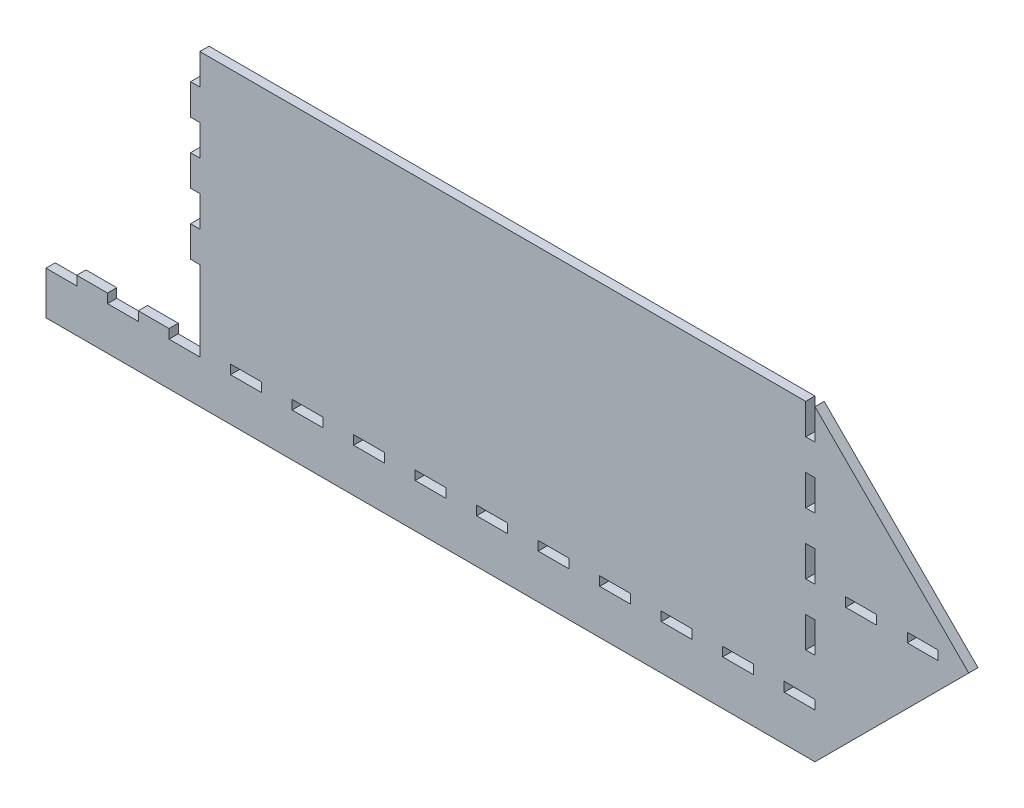
SolidWorks part; units mm, degrees
ref_plane "Front Plane" through (0, 0, 0) normal (0, 0, 1) x (1, 0, 0)
ref_plane "Top Plane" through (0, 0, 0) normal (0, 1, 0) x (1, 0, 0)
ref_plane "Right Plane" through (0, 0, 0) normal (1, 0, 0) x (0, 0, -1)
sketch "Sketch1" plane through (0, 0, 0) normal (0, 0, 1) x (1, 0, 0)
  line L0 (-112.631, -67.7284) -> (-112.631, -53.7284)
  line L1 (-62.631, 22.2716) -> (-65.631, 22.2716)
  line L2 (-102.631, -50.7284) -> (-92.631, -50.7284)
  line L3 (-62.631, 32.2716) -> (137.369, 32.2716)
  line L4 (137.369, 32.2716) -> (187.369, -17.7284)
  line L5 (187.369, -17.7284) -> (137.369, -67.7284)
  line L6 (137.369, -67.7284) -> (-112.631, -67.7284)
  line L7 (-65.631, 22.2716) -> (-65.631, 12.2716)
  line L8 (-62.631, -50.7284) -> (-62.631, -27.7284)
  line L9 (137.369, 32.2716) -> (137.369, -67.7284) construction
  line L10 (137.369, -17.7284) -> (187.369, -17.7284) construction
  line L11 (157.369, -16.2284) -> (147.369, -16.2284)
  line L12 (177.369, -16.2284) -> (167.369, -16.2284)
  line L13 (177.369, -16.2284) -> (177.369, -19.2284)
  line L14 (177.369, -19.2284) -> (167.369, -19.2284)
  line L15 (167.369, -16.2284) -> (167.369, -19.2284)
  line L16 (177.369, -16.2284) -> (167.369, -19.2284) construction
  line L17 (177.369, -19.2284) -> (167.369, -16.2284) construction
  line L18 (157.369, -16.2284) -> (157.369, -19.2284)
  line L19 (157.369, -19.2284) -> (147.369, -19.2284)
  line L20 (147.369, -16.2284) -> (147.369, -19.2284)
  line L21 (137.369, -50.1685) -> (127.369, -50.0127)
  line L22 (137.369, -50.1685) -> (137.369, -53.1358)
  line L23 (137.369, -53.1358) -> (127.369, -53.1358)
  line L24 (127.369, -50.0127) -> (127.369, -53.1358)
  line L25 (137.369, -50.1685) -> (127.369, -53.1358) construction
  line L26 (137.369, -53.1358) -> (127.369, -50.0127) construction
  line L27 (117.369, -50.1845) -> (107.369, -50.1845)
  line L28 (117.369, -50.1845) -> (117.369, -53.1845)
  line L29 (117.369, -53.1845) -> (107.369, -53.1845)
  line L30 (107.369, -50.1845) -> (107.369, -53.1845)
  line L31 (117.369, -50.1845) -> (107.369, -53.1845) construction
  line L32 (117.369, -53.1845) -> (107.369, -50.1845) construction
  line L33 (97.369, -50.2525) -> (87.369, -50.2525)
  line L34 (97.369, -50.2525) -> (97.369, -53.2525)
  line L35 (97.369, -53.2525) -> (87.369, -53.2525)
  line L36 (87.369, -50.2525) -> (87.369, -53.2525)
  line L37 (97.369, -50.2525) -> (87.369, -53.2525) construction
  line L38 (97.369, -53.2525) -> (87.369, -50.2525) construction
  line L39 (77.369, -50.3205) -> (67.369, -50.3205)
  line L40 (77.369, -50.3205) -> (77.369, -53.3205)
  line L41 (77.369, -53.3205) -> (67.369, -53.3205)
  line L42 (67.369, -50.3205) -> (67.369, -53.3205)
  line L43 (77.369, -50.3205) -> (67.369, -53.3205) construction
  line L44 (77.369, -53.3205) -> (67.369, -50.3205) construction
  line L45 (57.369, -50.3885) -> (47.369, -50.3885)
  line L46 (57.369, -50.3885) -> (57.369, -53.3885)
  line L47 (57.369, -53.3885) -> (47.369, -53.3885)
  line L48 (47.369, -50.3885) -> (47.369, -53.3885)
  line L49 (57.369, -50.3885) -> (47.369, -53.3885) construction
  line L50 (57.369, -53.3885) -> (47.369, -50.3885) construction
  line L51 (37.369, -50.4564) -> (27.369, -50.4564)
  line L52 (37.369, -50.4564) -> (37.369, -53.4564)
  line L53 (37.369, -53.4564) -> (27.369, -53.4564)
  line L54 (27.369, -50.4564) -> (27.369, -53.4564)
  line L55 (37.369, -50.4564) -> (27.369, -53.4564) construction
  line L56 (37.369, -53.4564) -> (27.369, -50.4564) construction
  line L57 (17.369, -50.5244) -> (7.369, -50.5244)
  line L58 (17.369, -50.5244) -> (17.369, -53.5244)
  line L59 (17.369, -53.5244) -> (7.369, -53.5244)
  line L60 (7.369, -50.5244) -> (7.369, -53.5244)
  line L61 (17.369, -50.5244) -> (7.369, -53.5244) construction
  line L62 (17.369, -53.5244) -> (7.369, -50.5244) construction
  line L63 (-2.631, -50.5924) -> (-12.631, -50.5924)
  line L64 (-2.631, -50.5924) -> (-2.631, -53.5924)
  line L65 (-2.631, -53.5924) -> (-12.631, -53.5924)
  line L66 (-12.631, -50.5924) -> (-12.631, -53.5924)
  line L67 (-2.631, -50.5924) -> (-12.631, -53.5924) construction
  line L68 (-2.631, -53.5924) -> (-12.631, -50.5924) construction
  line L69 (-22.631, -50.6604) -> (-32.631, -50.6604)
  line L70 (-22.631, -50.6604) -> (-22.631, -53.6604)
  line L71 (-22.631, -53.6604) -> (-32.631, -53.6604)
  line L72 (-32.631, -50.6604) -> (-32.631, -53.6604)
  line L73 (-22.631, -50.6604) -> (-32.631, -53.6604) construction
  line L74 (-22.631, -53.6604) -> (-32.631, -50.6604) construction
  line L75 (-42.631, -50.7284) -> (-52.631, -50.7284)
  line L76 (-42.631, -50.7284) -> (-42.631, -53.7284)
  line L77 (-42.631, -53.7284) -> (-52.631, -53.7284)
  line L78 (-52.631, -50.7284) -> (-52.631, -53.7284)
  line L79 (-42.631, -50.7284) -> (-52.631, -53.7284) construction
  line L80 (-42.631, -53.7284) -> (-52.631, -50.7284) construction
  line L81 (-82.631, -50.7284) -> (-72.631, -50.7284)
  line L82 (-62.631, -50.7284) -> (-62.631, -53.7284)
  line L83 (-62.631, -53.7284) -> (-72.631, -53.7284)
  line L84 (-72.631, -50.7284) -> (-72.631, -53.7284)
  line L85 (-62.631, -50.7284) -> (-72.631, -53.7284) construction
  line L86 (-62.631, -53.7284) -> (-72.631, -50.7284) construction
  line L87 (137.369, 12.2716) -> (134.369, 12.2716)
  line L88 (-82.631, -50.7284) -> (-82.631, -53.7284)
  line L89 (-82.631, -53.7284) -> (-92.631, -53.7284)
  line L90 (-92.631, -50.7284) -> (-92.631, -53.7284)
  line L91 (-82.631, -50.7284) -> (-92.631, -53.7284) construction
  line L92 (-82.631, -53.7284) -> (-92.631, -50.7284) construction
  line L93 (137.369, 32.2716) -> (134.369, 32.2716)
  line L94 (-102.631, -50.7284) -> (-102.631, -53.7284)
  line L95 (-102.631, -53.7284) -> (-112.631, -53.7284)
  line L96 (-65.631, 12.2716) -> (-62.631, 12.2716)
  line L97 (-102.631, -50.7284) -> (-112.631, -53.7284) construction
  line L98 (-102.631, -53.7284) -> (-112.631, -50.7284) construction
  line L99 (-62.631, -50.7284) -> (-72.631, -50.7284) [skipped]
  line L100 (-82.631, -50.7284) -> (-92.631, -50.7284) [skipped]
  line L101 (-102.631, -50.7284) -> (-112.631, -50.7284) [skipped]
  line L102 (137.369, 32.2716) -> (137.369, 22.2716)
  line L103 (137.369, 22.2716) -> (134.369, 22.2716)
  line L104 (134.369, 32.2716) -> (134.369, 22.2716)
  line L105 (137.369, 12.2716) -> (137.369, 2.2716)
  line L106 (137.369, 2.2716) -> (134.369, 2.2716)
  line L107 (134.369, 12.2716) -> (134.369, 2.2716)
  line L108 (137.369, -7.7284) -> (134.369, -7.7284)
  line L109 (137.369, -7.7284) -> (137.369, -17.7284)
  line L110 (-62.631, 2.2716) -> (-65.631, 2.2716)
  line L111 (137.369, -17.7284) -> (134.369, -17.7284)
  line L113 (-65.631, 2.2716) -> (-65.631, -7.7284)
  line L114 (157.369, -16.2284) -> (147.369, -19.2284) construction
  line L115 (-65.631, -7.7284) -> (-62.631, -7.7284)
  line L116 (-62.631, 2.2716) -> (-62.631, 12.2716)
  line L117 (-62.631, -17.7284) -> (-65.631, -17.7284)
  line L118 (-65.631, -17.7284) -> (-65.631, -27.7284)
  line L119 (-65.631, -27.7284) -> (-62.631, -27.7284)
  line L120 (-62.631, -17.7284) -> (-62.631, -7.7284)
  line L121 (134.369, -7.7284) -> (134.369, -17.7284)
  line L122 (157.369, -19.2284) -> (147.369, -16.2284) construction
  line L123 (-62.631, 22.2716) -> (-62.631, 32.2716)
  line L125 (-112.631, -52.2284) -> (-112.631, -53.3547) [skipped]
  line L128 (137.369, -27.7284) -> (134.369, -27.7284)
  line L129 (137.369, -27.7284) -> (137.369, -37.7284)
  line L130 (137.369, -37.7284) -> (134.369, -37.7284)
  line L131 (134.369, -27.7284) -> (134.369, -37.7284)
  point P5 (172.369, -17.7284)
  point P9 (151.1235, -51.5486)
  point P17 (152.369, -17.7284)
  point P19 (131.1235, -51.6165)
  point P24 (111.1235, -51.6845)
  point P29 (91.1235, -51.7525)
  point P34 (71.1235, -51.8205)
  point P39 (51.1235, -51.8885)
  point P44 (31.1235, -51.9564)
  point P49 (11.1235, -52.0244)
  point P54 (-8.8765, -52.0924)
  point P59 (-28.8765, -52.1604)
  point P64 (-48.8765, -52.2284)
  point P70 (-68.8765, -52.2284)
  point P75 (-88.8765, -52.2284)
  point P80 (-108.8765, -52.2284)
  dimension "D1" = 100
  dimension "D3" = 300
  dimension "D4" = 3
  dimension "D5" = 50
  dimension "D6" = 10
  dimension "D7" = 10
  dimension "D8" = 10
  dimension "D10" = 3
  dimension "D11" = 14
  dimension "D13" = 3
  dimension "D14" = 10
  dimension "D15" = 3
  dimension "D17" = 10
  dimension "D18" = 3
  dimension "D19" = 3
  dimension "D21" = 10
  dimension "D22" = 10
  dimension "D23" = 10
  dimension "D24" = 10
  dimension "D25" = 10
  dimension "D26" = 10
  dimension "D9" = 10
  dimension "D27" = 10
  dimension "D28" = 10
  dimension "D29" = 10
  dimension "D30" = 10
  dimension "D31" = 10
  dimension "D32" = 10
  dimension "D33" = 10
  dimension "D34" = 10
  dimension "D35" = 10
  dimension "D36" = 10
  dimension "D37" = 10
  dimension "D38" = 10
  dimension "D39" = 10
  dimension "D40" = 3
  dimension "D41" = 3
  dimension "D12" = 4
  dimension "D16" = 4
extrude "Boss-Extrude1" add sketch "Sketch1" along normal blind 3 contours L94 L95 L0 L6 L5 L4 L3 L82 L83 L84 L81 L88 L89 L90 L2 L24 L21 L22 L23 L30 L27 L28 L29 L36 L33 L34 L35 L42 L39 L40 L41 L48 L45 L46 L47 region at (44.6568, -18.7055, 0)
